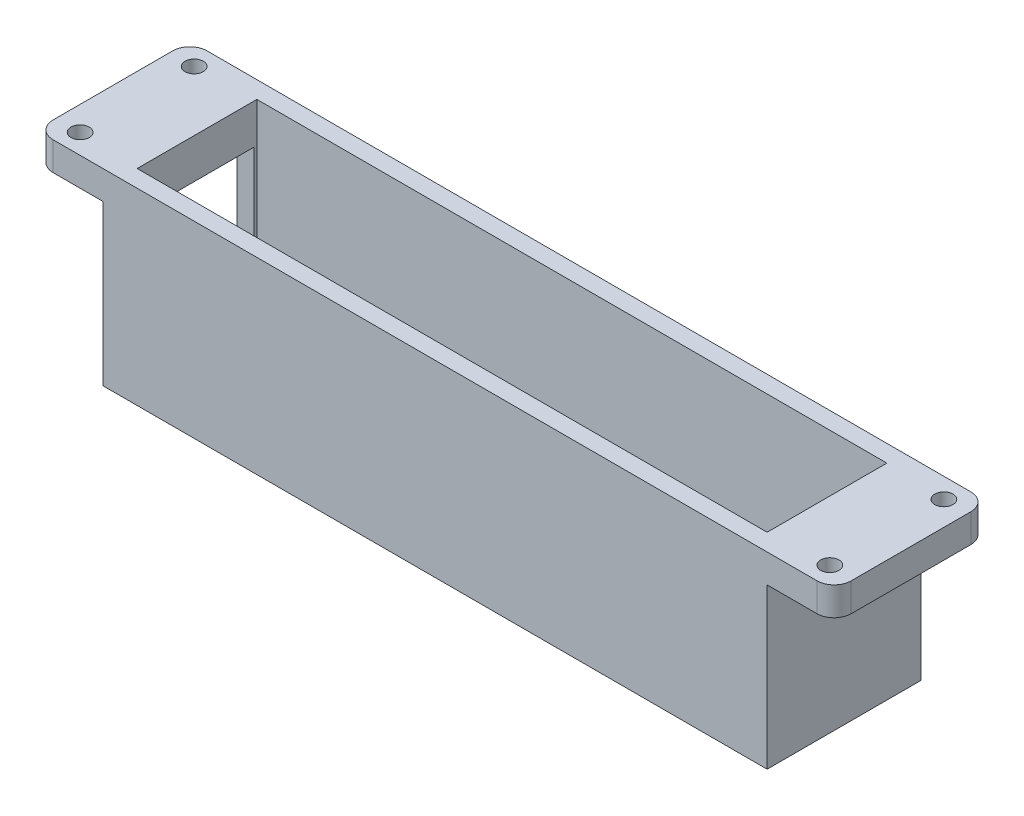
SolidWorks part; units mm, degrees
ref_plane "Płaszczyzna przednia" through (0, 0, 0) normal (0, 0, 1) x (1, 0, 0)
ref_plane "Płaszczyzna górna" through (0, 0, 0) normal (0, 1, 0) x (1, 0, 0)
ref_plane "Płaszczyzna prawa" through (0, 0, 0) normal (1, 0, 0) x (0, 0, -1)
sketch "Szkic1" plane through (0, 0, 0) normal (0, 0, 1) x (1, 0, 0)
  line L1 (0, 0) -> (116.5, 0)
  line L2 (0, 0) -> (0, 28)
  line L4 (116.5, 0) -> (116.5, 28)
  line L5 (-11.75, 33) -> (-11.75, 28)
  line L6 (-11.75, 28) -> (0, 28)
  line L8 (128.25, 33) -> (128.25, 28)
  line L9 (128.25, 28) -> (116.5, 28)
  line L10 (128.25, 33) -> (-11.75, 33)
  dimension "D1" = 116.5
  dimension "D2" = 140
  dimension "D4" = 28
  dimension "D5" = 5
  dimension "D6" = 5
extrude "Dodanie-wyciągnięcie1" add sketch "Szkic1" along normal blind 27
sketch "Szkic2" plane through (0, 33, 0) normal (0, 1, 0) x (1, 0, 0)
  line L0 (128.25, 0) -> (-11.75, 0) construction
  line L1 (3, -3) -> (113.5, -3)
  line L2 (3, -3) -> (3, -24)
  line L3 (3, -24) -> (113.5, -24)
  line L4 (113.5, -3) -> (113.5, -24)
  line L6 (58.25, 0) -> (58.25, -27) construction
  line L7 (128.25, -27) -> (-11.75, -27) construction
  line L8 (58.25, -3) -> (58.25, -24) construction
  dimension "D1" = 21
  dimension "D2" = 110.5
  dimension "D3" = 3
extrude "Wytnij-wyciągnięcie1" cut sketch "Szkic2" against normal offset from surface (30 mm away) 3 up to face at (58.25, 0, 13.5)
sketch "Szkic4" plane through (0, 0, 0) normal (-1, 0, 0) x (0, 0, 1)
  line L0 (27, 0) -> (0, 0) construction
  line L1 (3.5, 26) -> (23.5, 26)
  line L2 (3.5, 26) -> (3.5, 6)
  line L3 (3.5, 6) -> (23.5, 6)
  line L4 (23.5, 26) -> (23.5, 6)
  line L5 (0, 28) -> (0, 0) construction
  dimension "D1" = 20
  dimension "D2" = 20
  dimension "D3" = 6
  dimension "D4" = 3.5
extrude "Wytnij-wyciągnięcie3" cut sketch "Szkic4" against normal blind 3
sketch "Szkic5" plane through (0, 33, 0) normal (0, 1, 0) x (1, 0, 0)
  line L0 (128.25, 0) -> (-11.75, 0) construction
  line L1 (-11.75, -27) -> (-11.75, 0) construction
  line L2 (128.25, -27) -> (128.25, 0) construction
  circle A0 centre (-7.5, -3.5) radius 1.6
  circle A1 centre (124, -3.5) radius 1.6
  circle A2 centre (124, -23.5) radius 1.6
  circle A3 centre (-7.5, -23.5) radius 1.6
  dimension "D1" = 3.2
  dimension "D3" = 4.25
  dimension "D6" = 20
  dimension "D7" = 4.25
  dimension "D8" = 4.25
  dimension "D2" = 3.5
  dimension "D4" = 2
  dimension "D5" = 2
extrude "Wytnij-wyciągnięcie4" cut sketch "Szkic5" against normal through all
fillet "Fillet1" radius 3 4 edges at (128.25, 30.5, 0) (128.25, 30.5, 27) (-11.75, 30.5, 0) (-11.75, 30.5, 27)
